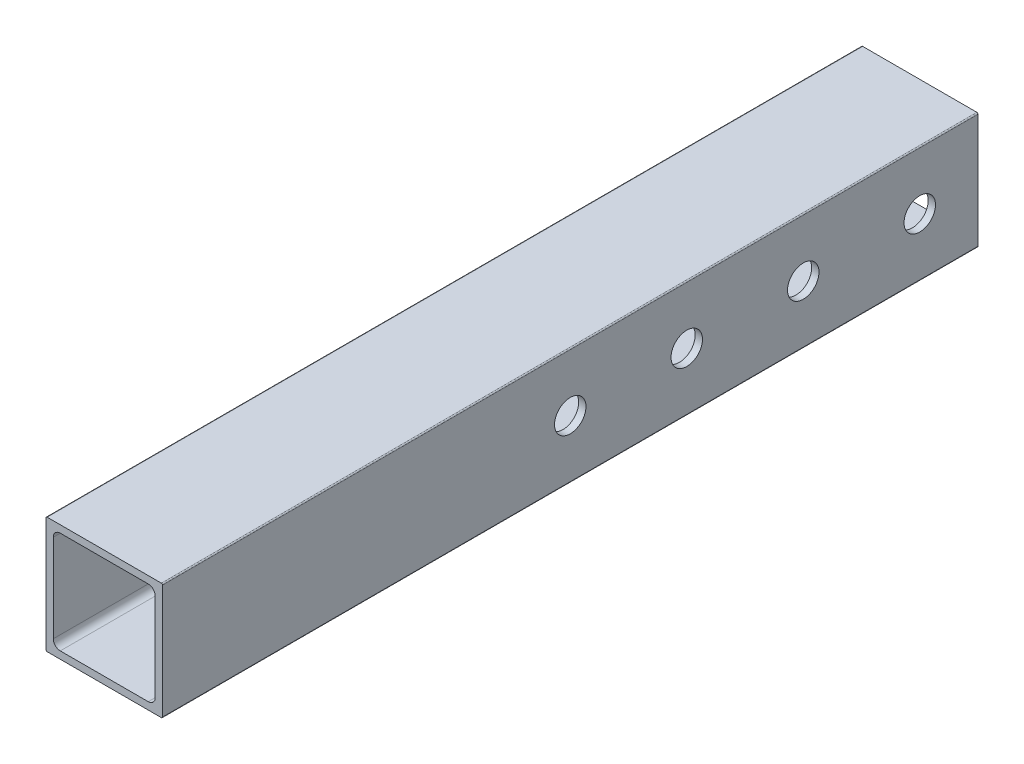
SolidWorks part; units mm, degrees
ref_plane "Front Plane" through (0, 0, 0) normal (0, 0, 1) x (1, 0, 0)
ref_plane "Top Plane" through (0, 0, 0) normal (0, 1, 0) x (1, 0, 0)
ref_plane "Right Plane" through (0, 0, 0) normal (1, 0, 0) x (0, 0, -1)
sketch "Sketch1" plane through (0, 0, 0) normal (0, 0, 1) x (1, 0, 0)
  line L0 (-9.5885, 11.1125) -> (9.5885, 11.1125)
  line L1 (-12.446, -12.7) -> (12.446, -12.7)
  line L2 (-12.7, -12.446) -> (-12.7, 12.446)
  line L3 (-12.446, 12.7) -> (12.446, 12.7)
  line L4 (12.7, -12.446) -> (12.7, 12.446)
  line L5 (-12.7, -12.7) -> (12.7, 12.7) construction
  line L6 (-12.7, 12.7) -> (12.7, -12.7) construction
  line L7 (11.1125, -9.5885) -> (11.1125, 9.5885)
  line L8 (-9.5885, -11.1125) -> (9.5885, -11.1125)
  line L9 (-11.1125, -9.5885) -> (-11.1125, 9.5885)
  line L10 (-12.7, -12.7) -> (12.7, -12.7) construction
  line L11 (-12.7, -12.7) -> (-12.7, 12.7) construction
  line L12 (12.7, -12.7) -> (12.7, 12.7) construction
  line L13 (-12.7, 12.7) -> (12.7, 12.7) construction
  line L14 (-11.1125, -11.1125) -> (11.1125, -11.1125) construction
  line L15 (-11.1125, -11.1125) -> (-11.1125, 11.1125) construction
  line L16 (11.1125, -11.1125) -> (11.1125, 11.1125) construction
  line L17 (-11.1125, 11.1125) -> (11.1125, 11.1125) construction
  arc A0 (-12.446, -12.7) -> (-12.7, -12.446) centre (-12.446, -12.446) cw
  arc A1 (12.446, -12.7) -> (12.7, -12.446) centre (12.446, -12.446) ccw
  arc A2 (12.446, 12.7) -> (12.7, 12.446) centre (12.446, 12.446) cw
  arc A3 (-12.7, 12.446) -> (-12.446, 12.7) centre (-12.446, 12.446) cw
  arc A4 (-9.5885, -11.1125) -> (-11.1125, -9.5885) centre (-9.5885, -9.5885) cw
  arc A5 (11.1125, -9.5885) -> (9.5885, -11.1125) centre (9.5885, -9.5885) cw
  arc A6 (9.5885, 11.1125) -> (11.1125, 9.5885) centre (9.5885, 9.5885) cw
  arc A7 (-9.5885, 11.1125) -> (-11.1125, 9.5885) centre (-9.5885, 9.5885) ccw
  point P0 (0, 0)
  dimension "D3" = 0.254
  dimension "D4" = 1.524
  dimension "D1" = 25.4
  dimension "D2" = 1.5875
extrude "Boss-Extrude1" add sketch "Sketch1" along normal blind 88.9 and the other way blind 88.9
sketch "Sketch2" plane through (-12.7, 0, 0) normal (-1, 0, 0) x (0, 0, 1)
  line L0 (-88.9, 0) -> (88.9, 0) construction
  line L1 (-88.9, 12.446) -> (-88.9, -12.446) construction
  line L2 (88.9, 12.446) -> (88.9, -12.446) construction
  circle A0 centre (-76.2, 0) radius 3.429
  circle A1 centre (-50.8, 0) radius 3.429
  circle A2 centre (-25.4, 0) radius 3.429
  circle A3 centre (0, 0) radius 3.429
  dimension "D1" = 6.858
  dimension "D2" = 12.7
  dimension "D4" = 25.4
  dimension "D3" = 4
extrude "Cut-Extrude1" cut sketch "Sketch2" against normal through all
